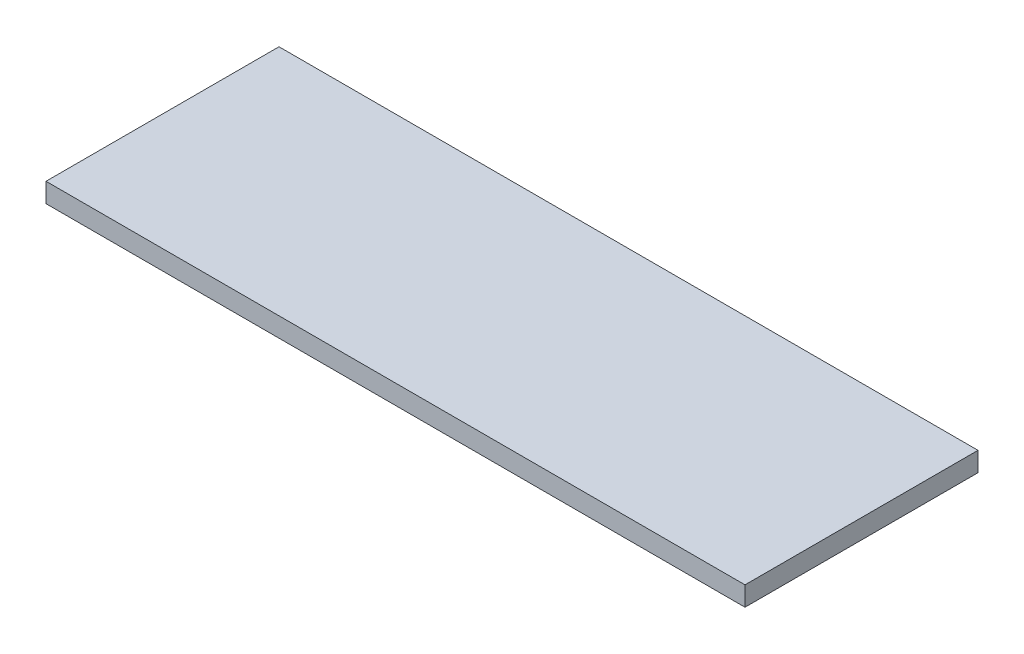
SolidWorks part; units mm, degrees
ref_plane "Front Plane" through (0, 0, 0) normal (0, 0, 1) x (1, 0, 0)
ref_plane "Top Plane" through (0, 0, 0) normal (0, 1, 0) x (1, 0, 0)
ref_plane "Right Plane" through (0, 0, 0) normal (1, 0, 0) x (0, 0, -1)
sketch "Sketch1" plane through (0, 0, 0) normal (0, 1, 0) x (1, 0, 0)
  line L1 (0, 0) -> (114.3, 0)
  line L2 (0, 0) -> (0, 38.1)
  line L3 (0, 38.1) -> (114.3, 38.1)
  line L4 (114.3, 0) -> (114.3, 38.1)
  dimension "D1" = 114.3
  dimension "D2" = 38.1
extrude "Boss-Extrude1" add sketch "Sketch1" along normal blind 3.175
